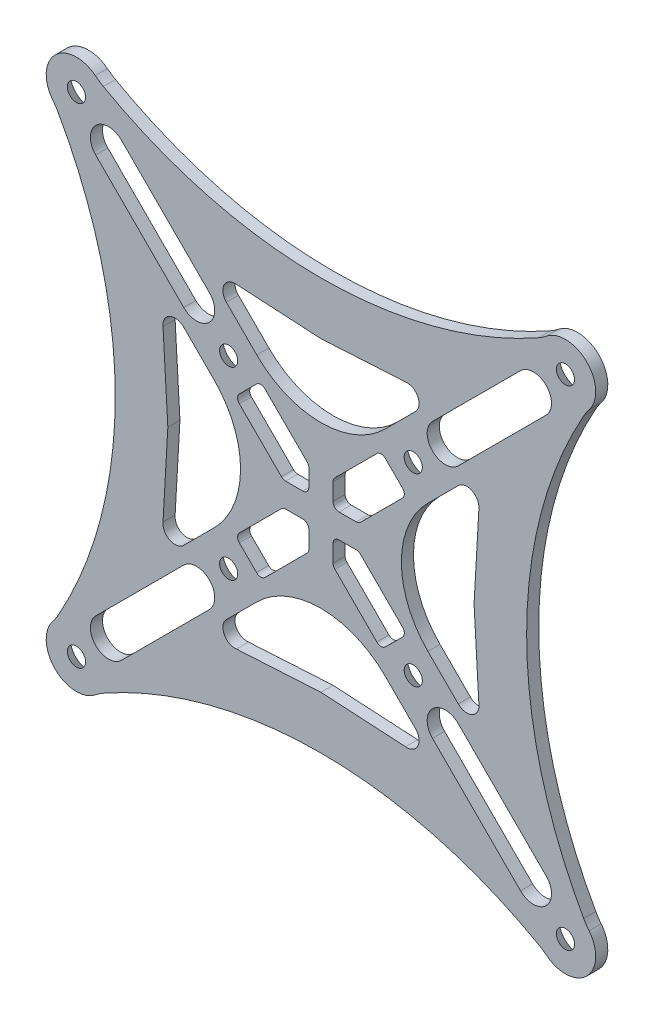
SolidWorks part; units mm, degrees
material "Thornel Mat VMA"
ref_plane "前视基准面" through (0, 0, 0) normal (0, 0, 1) x (1, 0, 0)
ref_plane "上视基准面" through (0, 0, 0) normal (0, 1, 0) x (1, 0, 0)
ref_plane "右视基准面" through (0, 0, 0) normal (1, 0, 0) x (0, 0, -1)
sketch "草图1" plane through (0, 0, 0) normal (0, 0, 1) x (1, 0, 0)
  line L0 (-33.5042, 37.1805) -> (-18.9606, 22.6369)
  line L1 (-23.2032, 18.3942) -> (-37.7469, 32.9379)
  line L2 (15.0968, 22.6587) -> (10.078, 17.6399)
  line L3 (17.9034, 22.6369) -> (32.447, 37.1805)
  line L4 (36.6896, 32.9379) -> (22.146, 18.3942)
  line L5 (-16.154, 22.6587) -> (-11.1352, 17.6399)
  line L6 (12.6001, -8.9238) -> (12.9536, -9.2773)
  line L7 (12.9536, -10.6916) -> (11.5394, -12.1058)
  line L8 (11.5394, -12.1058) -> (10.1252, -13.52)
  line L9 (8.711, -13.52) -> (8.3574, -13.1664)
  line L10 (8.3574, -13.1664) -> (5.5498, -10.3588)
  line L11 (5.5498, -10.3588) -> (1.7643, -6.5733)
  line L12 (1.4714, -5.8662) -> (1.4714, -3.0378)
  line L13 (2.4714, -2.0378) -> (5.2998, -2.0378)
  line L14 (6.0069, -2.3307) -> (9.7925, -6.1162)
  line L15 (9.7925, -6.1162) -> (12.6001, -8.9238)
  line L16 (10.1252, 13.4445) -> (11.5394, 12.0303)
  line L17 (11.5394, 12.0303) -> (12.9536, 10.616)
  line L18 (12.9536, 9.2018) -> (12.6001, 8.8483)
  line L19 (12.6001, 8.8483) -> (9.7925, 6.0407)
  line L20 (9.7925, 6.0407) -> (6.0069, 2.2551)
  line L21 (5.2998, 1.9622) -> (2.4714, 1.9622)
  line L22 (1.4714, 2.9622) -> (1.4714, 5.7907)
  line L23 (1.7643, 6.4978) -> (5.5498, 10.2833)
  line L24 (5.5498, 10.2833) -> (8.3574, 13.0909)
  line L25 (8.3574, 13.0909) -> (8.711, 13.4445)
  line L26 (17.1491, -10.6444) -> (22.1679, -15.6632)
  line L27 (15.0968, -22.7342) -> (10.078, -17.7154)
  line L28 (22.146, -18.4697) -> (36.6896, -33.0134)
  line L29 (32.447, -37.256) -> (17.9034, -22.7124)
  line L30 (-23.2032, -18.4697) -> (-37.7469, -33.0134)
  line L31 (-16.154, -22.7342) -> (-11.1352, -17.7154)
  line L32 (-11.1824, -13.52) -> (-12.5966, -12.1058)
  line L33 (-12.5966, -12.1058) -> (-14.0108, -10.6916)
  line L34 (-14.0108, -9.2773) -> (-13.6573, -8.9238)
  line L35 (-13.6573, -8.9238) -> (-10.8497, -6.1162)
  line L36 (-10.8497, -6.1162) -> (-7.0641, -2.3307)
  line L37 (-6.357, -2.0378) -> (-3.5286, -2.0378)
  line L38 (-2.5286, -3.0378) -> (-2.5286, -5.8662)
  line L39 (-2.8215, -6.5733) -> (-6.607, -10.3588)
  line L40 (-6.607, -10.3588) -> (-9.4146, -13.1664)
  line L41 (-9.4146, -13.1664) -> (-9.7682, -13.52)
  line L42 (-33.5042, -37.256) -> (-18.9606, -22.7124)
  line L43 (-18.2063, -10.6444) -> (-23.2251, -15.6632)
  line L44 (17.1491, 10.5688) -> (22.1679, 15.5877)
  line L45 (-14.0108, 10.616) -> (-12.5966, 12.0303)
  line L46 (-12.5966, 12.0303) -> (-11.1824, 13.4445)
  line L47 (-9.7682, 13.4445) -> (-9.4146, 13.0909)
  line L48 (-9.4146, 13.0909) -> (-6.607, 10.2833)
  line L49 (-6.607, 10.2833) -> (-2.8215, 6.4978)
  line L50 (-2.5286, 5.7907) -> (-2.5286, 2.9622)
  line L51 (-3.5286, 1.9622) -> (-6.357, 1.9622)
  line L52 (-7.0641, 2.2551) -> (-10.8497, 6.0407)
  line L53 (-10.8497, 6.0407) -> (-13.6573, 8.8483)
  line L54 (-13.6573, 8.8483) -> (-14.0108, 9.2018)
  line L55 (-18.2063, 10.5688) -> (-23.2251, 15.5877)
  arc A0 (-11.1352, 17.6399) -> (-0.5286, 13.2465) centre (-0.5286, 28.2465) ccw
  circle A1 centre (14.7214, 15.2122) radius 1.5
  circle A2 centre (-40.9288, 40.3625) radius 3
  circle A3 centre (14.7214, 15.2122) radius 3
  circle A4 centre (-40.9288, 40.3625) radius 1.5
  circle A5 centre (-40.9288, 40.3625) radius 3
  circle A6 centre (-15.7786, 15.2122) radius 3
  circle A7 centre (-40.9288, 40.3625) radius 1.5
  circle A8 centre (39.8716, 40.3625) radius 1.5
  circle A9 centre (39.8716, 40.3625) radius 3
  arc A10 (-23.2251, 15.5877) -> (-26.626, 13.9434) centre (-24.6393, 14.1734) ccw
  circle A11 centre (-15.7786, 15.2122) radius 1.5
  arc A12 (-0.5286, 13.2465) -> (10.078, 17.6399) centre (-0.5286, 28.2465) ccw
  arc A13 (15.0968, 22.6587) -> (13.4526, 26.0597) centre (13.6826, 24.0729) ccw
  arc A14 (-14.5098, 26.0597) -> (-16.154, 22.6587) centre (-14.7398, 24.0729) ccw
  arc A15 (-33.5042, 37.1805) -> (-37.7469, 32.9379) centre (-35.6255, 35.0592) ccw
  arc A16 (-23.2032, 18.3942) -> (-18.9606, 22.6369) centre (-21.0819, 20.5155) ccw
  arc A17 (17.9034, 22.6369) -> (22.146, 18.3942) centre (20.0247, 20.5155) ccw
  arc A18 (36.6896, 32.9379) -> (32.447, 37.1805) centre (34.5683, 35.0592) ccw
  arc A19 (25.5688, 13.9434) -> (22.1679, 15.5877) centre (23.5821, 14.1734) ccw
  arc A20 (12.9536, -10.6916) -> (12.9536, -9.2773) centre (12.2465, -9.9845) ccw
  arc A21 (8.711, -13.52) -> (10.1252, -13.52) centre (9.4181, -12.8129) ccw
  arc A22 (1.4714, -5.8662) -> (1.7643, -6.5733) centre (2.4714, -5.8662) ccw
  arc A23 (2.4714, -2.0378) -> (1.4714, -3.0378) centre (2.4714, -3.0378) ccw
  arc A24 (6.0069, -2.3307) -> (5.2998, -2.0378) centre (5.2998, -3.0378) ccw
  arc A25 (17.1491, 10.5688) -> (12.7557, -0.0378) centre (27.7557, -0.0378) ccw
  arc A26 (10.1252, 13.4445) -> (8.711, 13.4445) centre (9.4181, 12.7374) ccw
  arc A27 (12.9536, 9.2018) -> (12.9536, 10.616) centre (12.2465, 9.9089) ccw
  arc A28 (5.2998, 1.9622) -> (6.0069, 2.2551) centre (5.2998, 2.9622) ccw
  arc A29 (1.4714, 2.9622) -> (2.4714, 1.9622) centre (2.4714, 2.9622) ccw
  arc A30 (1.7643, 6.4978) -> (1.4714, 5.7907) centre (2.4714, 5.7907) ccw
  arc A31 (12.7557, -0.0378) -> (17.1491, -10.6444) centre (27.7557, -0.0378) ccw
  arc A32 (32.447, -37.256) -> (36.6896, -33.0134) centre (34.5683, -35.1347) ccw
  arc A33 (22.146, -18.4697) -> (17.9034, -22.7124) centre (20.0247, -20.5911) ccw
  arc A34 (-11.1824, -13.52) -> (-9.7682, -13.52) centre (-10.4753, -12.8129) ccw
  arc A35 (-14.0108, -9.2773) -> (-14.0108, -10.6916) centre (-13.3037, -9.9845) ccw
  arc A36 (-6.357, -2.0378) -> (-7.0641, -2.3307) centre (-6.357, -3.0378) ccw
  arc A37 (-2.5286, -3.0378) -> (-3.5286, -2.0378) centre (-3.5286, -3.0378) ccw
  arc A38 (-2.8215, -6.5733) -> (-2.5286, -5.8662) centre (-3.5286, -5.8662) ccw
  arc A39 (-16.154, -22.7342) -> (-14.5098, -26.1352) centre (-14.7398, -24.1484) ccw
  circle A40 centre (-40.9288, -40.438) radius 1.5
  arc A41 (-37.7469, -33.0134) -> (-33.5042, -37.256) centre (-35.6255, -35.1347) ccw
  arc A42 (-0.5286, -13.322) -> (-11.1352, -17.7154) centre (-0.5286, -28.322) ccw
  circle A43 centre (-15.7786, -15.2878) radius 1.5
  circle A44 centre (-15.7786, -15.2878) radius 3
  arc A45 (-18.9606, -22.7124) -> (-23.2032, -18.4697) centre (-21.0819, -20.5911) ccw
  arc A46 (-26.626, -14.0189) -> (-23.2251, -15.6632) centre (-24.6393, -14.249) ccw
  circle A47 centre (-40.9288, -40.438) radius 3
  circle A48 centre (39.8716, -40.438) radius 1.5
  arc A49 (22.1679, -15.6632) -> (25.5688, -14.0189) centre (23.5821, -14.249) ccw
  circle A50 centre (14.7214, -15.2878) radius 3
  arc A51 (10.078, -17.7154) -> (-0.5286, -13.322) centre (-0.5286, -28.322) ccw
  circle A52 centre (39.8716, -40.438) radius 3
  circle A53 centre (14.7214, -15.2878) radius 1.5
  arc A54 (13.4526, -26.1352) -> (15.0968, -22.7342) centre (13.6826, -24.1484) ccw
  arc A55 (-14.0108, 10.616) -> (-14.0108, 9.2018) centre (-13.3037, 9.9089) ccw
  arc A56 (-9.7682, 13.4445) -> (-11.1824, 13.4445) centre (-10.4753, 12.7374) ccw
  arc A57 (-2.5286, 5.7907) -> (-2.8215, 6.4978) centre (-3.5286, 5.7907) ccw
  arc A58 (-3.5286, 1.9622) -> (-2.5286, 2.9622) centre (-3.5286, 2.9622) ccw
  arc A59 (-7.0641, 2.2551) -> (-6.357, 1.9622) centre (-6.357, 2.9622) ccw
  arc A60 (-18.2063, -10.6444) -> (-13.8129, -0.0378) centre (-28.8129, -0.0378) ccw
  arc A61 (-13.8129, -0.0378) -> (-18.2063, 10.5688) centre (-28.8129, -0.0378) ccw
  arc A62 (-44.8386, -37.3214) -> (-37.8122, -44.3478) centre (-40.9288, -40.438) ccw
  arc A63 (36.755, -44.3478) -> (43.7814, -37.3214) centre (39.8716, -40.438) ccw
  arc A64 (43.7814, 37.2458) -> (36.755, 44.2723) centre (39.8716, 40.3625) ccw
  arc A65 (-37.8122, 44.2723) -> (-44.8386, 37.2458) centre (-40.9288, 40.3625) ccw
  arc A66 (-43.9442, -35.9938) -> (-43.9442, 35.9183) centre (-107.8132, -0.0378) ccw
  arc A67 (35.4274, -43.4534) -> (-36.4846, -43.4534) centre (-0.5286, -107.3223) ccw
  arc A68 (-36.4846, 43.3779) -> (35.4274, 43.3779) centre (-0.5286, 107.2468) ccw
  arc A69 (-37.8122, 44.2723) -> (-36.4846, 43.3779) centre (-31.5789, 52.0919) ccw
  arc A70 (-43.9442, 35.9183) -> (-44.8386, 37.2458) centre (-52.6583, 31.0126) ccw
  arc A71 (-44.8386, -37.3214) -> (-43.9442, -35.9938) centre (-52.6583, -31.0881) ccw
  arc A72 (-36.4846, -43.4534) -> (-37.8122, -44.3478) centre (-31.5789, -52.1674) ccw
  arc A73 (36.755, -44.3478) -> (35.4274, -43.4534) centre (30.5217, -52.1674) ccw
  arc A74 (42.887, -35.9938) -> (43.7814, -37.3214) centre (51.601, -31.0881) ccw
  arc A75 (35.4274, 43.3779) -> (36.755, 44.2723) centre (30.5217, 52.0919) ccw
  arc A76 (43.7814, 37.2458) -> (42.887, 35.9183) centre (51.601, 31.0126) ccw
  arc A77 (42.887, 35.9183) -> (42.887, -35.9938) centre (106.7559, -0.0378) ccw
  spline S0 degree 3 poles (-14.5098, 26.0597) (-9.8494, 25.7939) (-5.189, 25.5282) (-0.5286, 25.2624) knots 0 0 0 0 1.400387 1.400387 1.400387 1.400387
  spline S1 degree 3 poles (13.4526, 26.0597) (8.7922, 25.7939) (4.1318, 25.5282) (-0.5286, 25.2624) knots 0 0 0 0 1.400387 1.400387 1.400387 1.400387
  spline S2 degree 3 poles (25.5688, -14.0189) (25.3031, -9.3585) (25.0373, -4.6981) (24.7716, -0.0378) knots 0 0 0 0 1.400387 1.400387 1.400387 1.400387
  spline S3 degree 3 poles (25.5688, 13.9434) (25.3031, 9.283) (25.0373, 4.6226) (24.7716, -0.0378) knots 0 0 0 0 1.400387 1.400387 1.400387 1.400387
  spline S4 degree 3 poles (-14.5098, -26.1352) (-9.8494, -25.8694) (-5.189, -25.6037) (-0.5286, -25.3379) knots 0 0 0 0 1.400387 1.400387 1.400387 1.400387
  spline S5 degree 3 poles (13.4526, -26.1352) (8.7922, -25.8694) (4.1318, -25.6037) (-0.5286, -25.3379) knots 0 0 0 0 1.400387 1.400387 1.400387 1.400387
  spline S6 degree 3 poles (-26.626, 13.9434) (-26.3603, 9.283) (-26.0945, 4.6226) (-25.8288, -0.0378) knots 0 0 0 0 1.400387 1.400387 1.400387 1.400387
  spline S7 degree 3 poles (-26.626, -14.0189) (-26.3603, -9.3585) (-26.0945, -4.6981) (-25.8288, -0.0378) knots 0 0 0 0 1.400387 1.400387 1.400387 1.400387
  dimension "D1" = 6
extrude "凸台-拉伸1" add sketch "草图1" along normal blind 2 contours A77 A76 A64 A75 A68 A69 A65 A70 A66 A71 A62 A72 A67 A73 A63 A74 S1 A13 L2 A12 A0 L5 A14 S0 A59 L52 L53 L54 A55 L45 L46 A56 L47 L48 L49 A57 L50 A58 L51 A52 A50 A47 A45 L42 A41 | A2 A4 | A9 A8 | A50 A53 | A3 A1 | A6 A11 | A44 A43 | A47 A40 | A52 A48 region at (-43.844, 40.3625, 0) region at (11.8062, 15.2122, 0) region at (-18.6938, 15.2122, 0) region at (36.9565, 40.3625, 0) region at (-18.6938, -15.2878, 0) region at (-43.844, -40.438, 0) region at (11.8062, -15.2878, 0) region at (36.9565, -40.438, 0) region at (-0.5286, -0.0378, 0)
chamfer "倒角2" distance 2 distance2 1.5 8 edges at (-39.4288, 40.3625, 0) (-14.2786, -15.2878, 0) (16.2214, -15.2878, 0) (16.2214, 15.2122, 0) (-14.2786, 15.2122, 0) (-39.4288, -40.438, 0) (41.3716, -40.438, 0) (41.3716, 40.3625, 0) first distance on face at (-39.4288, 40.3625, 2) first distance on face at (-14.2786, -15.2878, 2) first distance on face at (16.2214, -15.2878, 2) first distance on face at (16.2214, 15.2122, 2) first distance on face at (-14.2786, 15.2122, 2) first distance on face at (-39.4288, -40.438, 2) first distance on face at (41.3716, -40.438, 2) first distance on face at (41.3716, 40.3625, 2)
